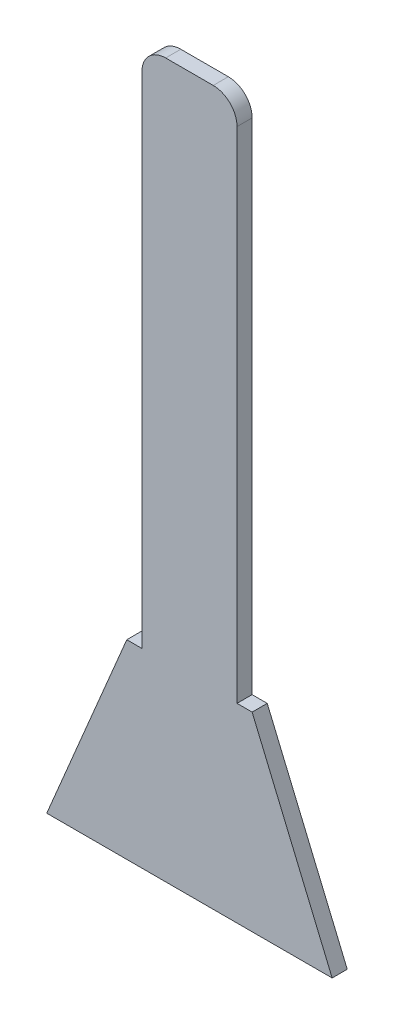
SolidWorks part; units mm, degrees
material "ABS"
ref_plane "Plan de face" through (0, 0, 0) normal (0, 0, 1) x (1, 0, 0)
ref_plane "Plan de dessus" through (0, 0, 0) normal (0, 1, 0) x (1, 0, 0)
ref_plane "Plan de droite" through (0, 0, 0) normal (1, 0, 0) x (0, 0, -1)
sketch "Esquisse1" plane through (0, 0, 0) normal (0, 0, 1) x (1, 0, 0)
  line L1 (-20, 300) -> (20, 300)
  line L2 (-20, 300) -> (-20, 80)
  line L4 (20, 300) -> (20, 80)
  line L8 (-60, 0) -> (60, 0)
  line L9 (26.35, 80) -> (-26.35, 80) construction
  line L10 (26.35, 80) -> (60, 0)
  line L11 (-26.35, 80) -> (-60, 0)
  line L12 (26.35, 80) -> (20, 80)
  line L13 (-20, 80) -> (-26.35, 80)
  point P1 (0, 0)
  point P2 (0, 300)
  point P8 (0, 80)
  dimension "D1" = 80
  dimension "D2" = 120
  dimension "D3" = 40
  dimension "D4" = 300
  dimension "D5" = 6.35
extrude "Boss.-Extru.1" add sketch "Esquisse1" along normal blind 6.35
fillet "Congé1" radius 10 2 edges at (20, 300, 3.175) (-20, 300, 3.175)
